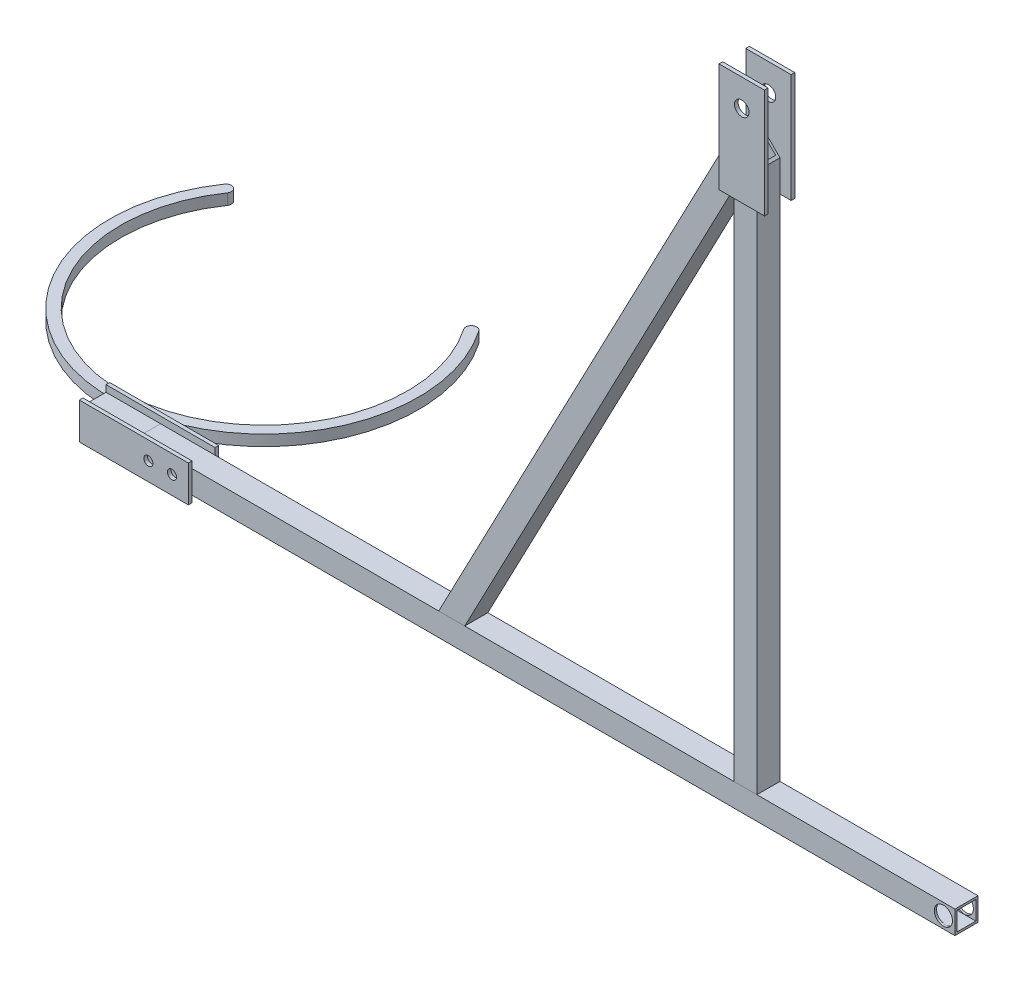
SolidWorks part; units mm, degrees
ref_plane "Front Plane" through (0, 0, 0) normal (0, 0, 1) x (1, 0, 0)
ref_plane "Top Plane" through (0, 0, 0) normal (0, 1, 0) x (1, 0, 0)
ref_plane "Right Plane" through (0, 0, 0) normal (1, 0, 0) x (0, 0, -1)
sketch "Sketch1" plane through (0, 0, 0) normal (0, 0, 1) x (1, 0, 0)
  line L0 (-115.35, 316.35) -> (-277.8308, 6.35)
  line L1 (-443.65, -6.35) -> (6.35, -6.35)
  line L2 (-443.65, -6.35) -> (-443.65, 6.35)
  line L3 (-443.65, 6.35) -> (6.35, 6.35)
  line L4 (6.35, -6.35) -> (6.35, 6.35)
  line L5 (-443.65, -6.35) -> (6.35, 6.35) construction
  line L6 (-443.65, 6.35) -> (6.35, -6.35) construction
  line L7 (6.35, 6.35) -> (-115.35, 6.35)
  line L10 (-115.35, 6.35) -> (-115.35, 316.35)
  line L11 (-115.35, 288.9929) -> (-263.4921, 6.35)
  line L12 (-104.1014, 310.4543) -> (-266.5822, 0.4543) construction
  line L13 (-109, 331.35) -> (334.7426, 6.4) construction
  line L14 (-96.5, 286.35) -> (-121.5, 286.35)
  line L15 (-96.5, 286.35) -> (-96.5, 346.35)
  line L16 (-96.5, 346.35) -> (-121.5, 346.35)
  line L17 (-121.5, 286.35) -> (-121.5, 346.35)
  line L18 (-115.35, 316.35) -> (-102.65, 303.65)
  line L19 (-102.65, 303.65) -> (-102.65, 6.35)
  circle A0 centre (-109, 331.35) radius 4
  circle A1 centre (0, 0) radius 5
  point P0 (-218.65, 0)
  point P21 (-109, 346.35)
  point P23 (-109, 310)
  dimension "D9" = 8
  dimension "D12" = 10
  dimension "D1" = 6.35
  dimension "D2" = 12.7
  dimension "D3" = 450
  dimension "D4" = 12.7
  dimension "D5" = 15
  dimension "D6" = 350
  dimension "D8" = 25
  dimension "D10" = 60
  dimension "D11" = 45
  dimension "D13" = 550
  dimension "D14" = 325
  dimension "D15" = 6.4
  dimension "D16" = 334.7426
  dimension "D17" = 15
  dimension "D18" = 109
  dimension "D19" = 310
  dimension "D7" = 12.7
extrude "Boss-Extrude1" add sketch "Sketch1" along normal mid plane 12.7 contours L1 L4 L3 L2 A1 | A1 region at (-221.6967, 0, 0) region at (0, 0, 0)
shell "Shell1" thickness 1.2 removed face at (-443.65, 0, 0) removed face at (6.35, 0, 0)
extrude "Boss-Extrude2" add sketch "Sketch1<3>" along normal mid plane 12.7 separate body contours L14 L17 L0 L3 L11 | L17 L14 L11 L10 L0 region at (-118.2053, 298.7969, 0) region at (-195.7357, 149.4639, 0)
sketch "Sketch1<3>" plane through (0, 0, 0) normal (0, 0, 1) x (1, 0, 0) same geometry as "Sketch1"
shell "Shell2" thickness 1.2 removed face at (-115.35, 302.6715, 0) removed face at (-270.6614, 6.35, 0)
extrude "Boss-Extrude3" add sketch "Sketch1<4>" along normal mid plane 12.7 separate body contours L14 L10 L3 | L14 L10 region at (-109.5683, 298.4592, 0) region at (-109, 146.35, 0)
sketch "Sketch1<4>" plane through (0, 0, 0) normal (0, 0, 1) x (1, 0, 0) same geometry as "Sketch1"
shell "Shell3" thickness 1.2 removed face at (-109, 6.35, 0) removed face at (-109, 310, 0)
extrude "Boss-Extrude4" add sketch "Sketch1<5>" along normal blind 2 from surface separate body contours L0 L18 L14 L15 L16 L17 A0 | L18 L10 L14 | L17 L14 L11 L10 L0 | L14 L10 L11 region at (-118.2053, 298.7969, 0) region at (-109.5683, 298.4592, 0) region at (-107.4689, 323.589, 0) region at (-115.8117, 287.231, 0) starting at face at (-193.0057, 154.5107, 6.35)
sketch "Sketch1<5>" plane through (0, 0, 0) normal (0, 0, 1) x (1, 0, 0) same geometry as "Sketch1"
mirror "Mirror1" about plane through (0, 0, 0) normal (0, 0, 1) of bodies 104
extrude "Cut-Extrude1" cut sketch "Sketch1<6>" against normal through all both and the other way through all contours A1
sketch "Sketch1<6>" plane through (0, 0, 0) normal (0, 0, 1) x (1, 0, 0) same geometry as "Sketch1"
sketch "Sketch2" plane through (0, 0, 6.35) normal (0, 0, 1) x (1, 0, 0)
  line L0 (-443.65, -6.35) -> (-443.65, 6.35) construction
  line L1 (-473.65, 10) -> (-413.65, 10)
  line L2 (-473.65, 10) -> (-473.65, -10)
  line L3 (-473.65, -10) -> (-413.65, -10)
  line L4 (-413.65, 10) -> (-413.65, -10)
  line L5 (-473.65, 10) -> (-413.65, -10) construction
  line L6 (-473.65, -10) -> (-413.65, 10) construction
  line L7 (-443.65, -6.35) -> (6.35, -6.35) construction
  line L8 (-443.65, 6.35) -> (-473.65, 6.35)
  line L9 (-443.65, 6.35) -> (-443.65, -6.35)
  line L10 (-443.65, -6.35) -> (-473.65, -6.35)
  line L11 (-473.65, 6.35) -> (-473.65, -6.35)
  circle A0 centre (-435.65, 0) radius 2.5
  circle A1 centre (-422.65, 0) radius 2.5
  point P0 (-443.65, 0)
  point P18 (0, 0)
  point P19 (0, 0)
  line M10 (-443.65, -6.35) -> (6.35, -6.35)
  line M12 (6.35, 6.35) -> (-443.65, 6.35)
  line M13 (-443.65, 6.35) -> (-443.65, -6.35)
  dimension "D3" = 5
  dimension "D4" = 5
  dimension "D1" = 60
  dimension "D2" = 20
  dimension "D5" = 13
  dimension "D6" = 8
extrude "Boss-Extrude5" add sketch "Sketch2" along normal blind 2 separate body contours L10 L2 L3 L4 M10 | L4 A1 A0 M12 M13 M10 | L10 L8 L2 M13 | L8 L4 L1 L2 M12 region at (-443.65, 8.175, 6.35) region at (-458.65, 0, 6.35) region at (-428.5925, 0, 6.35) region at (-443.65, -8.175, 6.35)
sketch "Sketch4" plane through (-443.65, 0, 0) normal (-1, 0, 0) x (0, 0, 1)
  line L0 (-5.15, -5.15) -> (-5.15, 5.15) construction
  line L1 (-5.15, -5.15) -> (-5.15, 5.15)
  line L2 (5.15, -5.15) -> (5.15, 5.15) construction
  line L3 (5.15, -5.15) -> (-5.15, -5.15) construction
  line L4 (-6.35, 6.35) -> (-6.35, -6.35)
  line L5 (-6.35, -6.35) -> (6.35, -6.35)
  line L6 (6.35, -6.35) -> (6.35, 6.35)
  line L7 (6.35, 6.35) -> (-6.35, 6.35)
  line L8 (-6.35, 6.35) -> (-6.35, -6.35)
  line L9 (-6.35, -6.35) -> (6.35, -6.35)
  line L10 (6.35, -6.35) -> (6.35, 6.35)
  line L11 (6.35, 6.35) -> (-6.35, 6.35)
  line L12 (5.15, 5.15) -> (-5.15, 5.15) construction
  line L13 (5.15, -5.15) -> (5.15, 5.15)
  line L14 (5.15, -5.15) -> (-5.15, -5.15)
  line L15 (5.15, 5.15) -> (-5.15, 5.15)
  dimension "D1" = 0
extrude "Boss-Extrude7" add sketch "Sketch4" along normal up to surface (30 mm away) separate body up to face at (-473.65, 0, 7.35)
extrude "Boss-Extrude8" add sketch "Sketch2<6>" against normal blind 2 from surface separate body contours L10 L2 L3 L4 M10 | L10 L8 L2 M13 | L4 A1 A0 M12 M13 M10 | L8 L4 L1 L2 M12 region at (-443.65, 8.175, 6.35) region at (-458.65, 0, 6.35) region at (-428.5925, 0, 6.35) region at (-443.65, -8.175, 6.35) starting at face at (-458.65, 0, -6.35)
sketch "Sketch2<6>" plane through (0, 0, 6.35) normal (0, 0, 1) x (1, 0, 0) same geometry as "Sketch2"
sketch "Sketch5" plane through (0, 0, 0) normal (0, 1, 0) x (1, 0, 0)
  line L0 (-543.65, 141.5683) -> (-403.65, 141.5683) construction
  line L1 (-433.15, 8.35) -> (-438.15, 8.35) construction
  arc A0 (-543.65, 141.5683) -> (-403.65, 141.5683) centre (-473.65, 93.35) ccw
  arc A1 (-538.7088, 138.1646) -> (-408.5912, 138.1646) centre (-473.65, 93.35) ccw
  arc A2 (-543.65, 141.5683) -> (-538.7088, 138.1646) centre (-541.1794, 139.8664) cw
  arc A3 (-403.65, 141.5683) -> (-408.5912, 138.1646) centre (-406.1206, 139.8664) ccw
  point P5 (0, 0)
  point P6 (-473.65, 8.35)
  point P7 (0, 0)
  point P9 (-410.1296, 133.4778)
  point P10 (-396.13, 151.0186)
  point P11 (-403.65, 49.6202)
  point P12 (-408.9272, 135.3708)
  dimension "D2" = 85
  dimension "D1" = 140
  dimension "D3" = 6
extrude "Boss-Extrude9" add sketch "Sketch5" along normal mid plane 6 separate body
